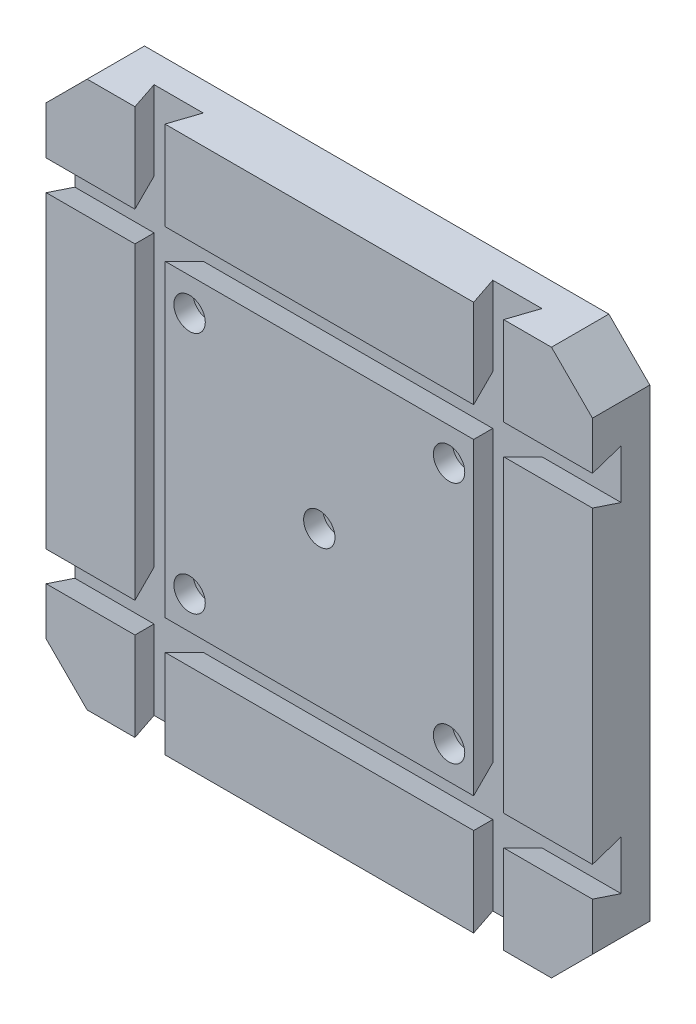
SolidWorks part; units mm, degrees
ref_plane "前视基准面" through (0, 0, 0) normal (0, 0, 1) x (1, 0, 0)
ref_plane "上视基准面" through (0, 0, 0) normal (0, 1, 0) x (1, 0, 0)
ref_plane "右视基准面" through (0, 0, 0) normal (1, 0, 0) x (0, 0, -1)
sketch "草图1" plane through (0, 0, 0) normal (0, 0, 1) x (1, 0, 0)
  line L1 (-200, -200) -> (200, -200)
  line L2 (-200, -200) -> (-200, 200)
  line L3 (-200, 200) -> (200, 200)
  line L4 (200, -200) -> (200, 200)
  line L5 (-200, -200) -> (200, 200) construction
  line L6 (-200, 200) -> (200, -200) construction
  point P0 (0, 0)
  dimension "D1" = 400
extrude "凸台-拉伸1" add sketch "草图1" along normal blind 42
chamfer "倒角1" distance 30 angle 45 4 edges at (-200, -200, 21) (-200, 200, 21) (200, 200, 21) (200, -200, 21)
sketch "草图2" plane through (0, -200, 0) normal (0, -1, 0) x (1, 0, 0)
  line L0 (0, 21) -> (-124, 21) construction
  line L1 (0, -23.1) -> (0, 23.1) construction
  line L2 (-170, 0) -> (170, 0) construction
  line L3 (-142, 21) -> (-106, 21)
  line L4 (-106, 21) -> (-113, 42)
  line L5 (-113, 42) -> (-135, 42)
  line L6 (-135, 42) -> (-142, 21)
  line L7 (-170, 42) -> (170, 42) construction
  point P9 (-124, 21)
  dimension "D1" = 124
  dimension "D2" = 21
  dimension "D3" = 22
  dimension "D4" = 36
extrude "切除-拉伸1" cut sketch "草图2" against normal through all both and the other way through all
mirror "镜向1" about plane through (0, 0, 0) normal (1, 0, 0) of "切除-拉伸1"
ref_axis "基准轴1" through (0, 0, -2.1) along (0, 0, 1)
pattern_circular "阵列(圆周)1" count 2 every 90 about axis through (0, 0, -2.1) along (0, 0, 1) of "镜向1"
sketch "草图4" plane through (0, 0, 42) normal (0, 0, 1) x (1, 0, 0)
  line L1 (-95, -89) -> (95, -89) construction
  line L2 (-95, -89) -> (-95, 89) construction
  line L3 (-95, 89) -> (95, 89) construction
  line L4 (95, -89) -> (95, 89) construction
  line L5 (-95, -89) -> (95, 89) construction
  line L6 (-95, 89) -> (95, -89) construction
  point P0 (0, 0)
  point P6 (95, 89)
  point P8 (95, -89)
  point P9 (-95, -89)
  point P10 (-95, 89)
  dimension "D1" = 178
  dimension "D2" = 190
hole_wizard "孔1" positions "草图4" profile "草图5" legacy end condition through all
sketch "草图5" plane through (0, 0, 42) normal (1, 0, 0) x (0, -1, 0)
  line L0 (0, 0) -> (0, 42)
  line L1 (0, 42) -> (6.5, 42)
  line L2 (6.5, 42) -> (6.5, 14)
  line L3 (6.5, 14) -> (11.5, 14)
  line L4 (11.5, 14) -> (11.5, 0)
  line L5 (11.5, 0) -> (0, 0)
  line L6 (0, 110) -> (0, -10) construction
  dimension "直径" = 13
  dimension "深度" = 42
  dimension "柱坑直径" = 23
  dimension "柱坑深度" = 14
